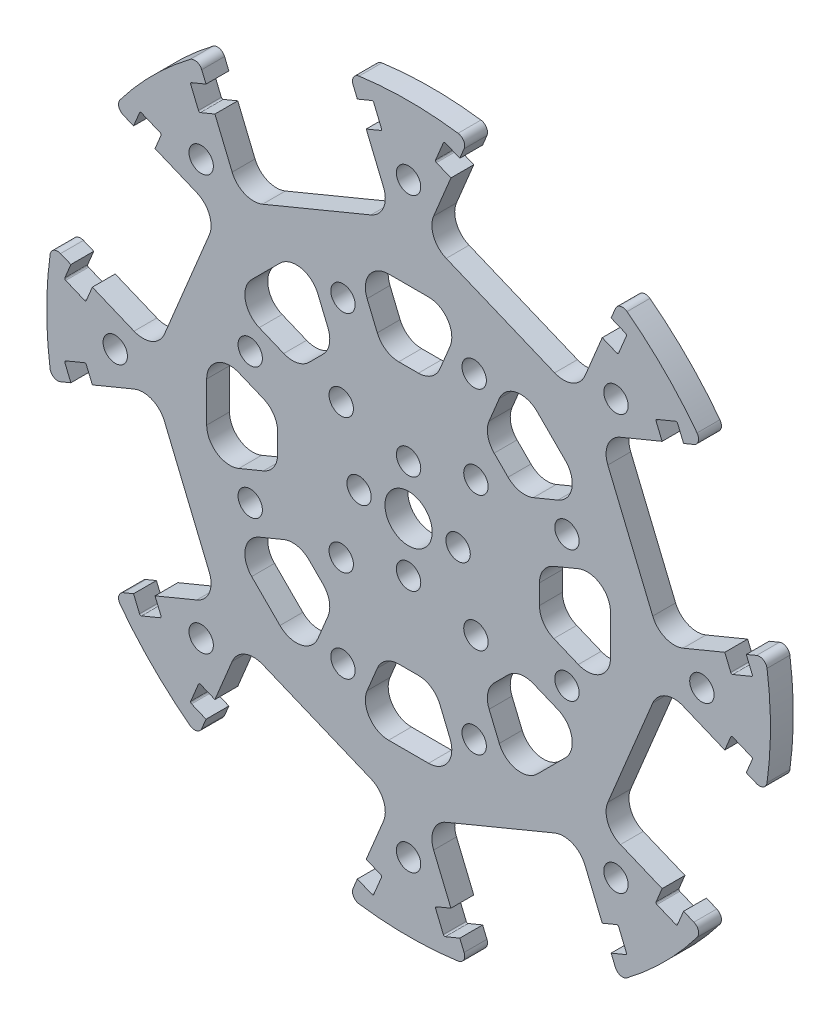
SolidWorks part; units mm, degrees
material "5052-H34"
ref_plane "正面" through (0, 0, 0) normal (0, 0, 1) x (1, 0, 0)
ref_plane "平面" through (0, 0, 0) normal (0, 1, 0) x (1, 0, 0)
ref_plane "右側面" through (0, 0, 0) normal (1, 0, 0) x (0, 0, -1)
sketch "ｽｹｯﾁ1" plane through (0, 0, 0) normal (0, 0, 1) x (1, 0, 0)
  circle A0 centre (0, 0) radius 47.5
  dimension "D1" = 95
extrude "ﾎﾞｽ - 押し出し1" add sketch "ｽｹｯﾁ1" along normal blind 3
sketch "ｽｹｯﾁ2" plane through (0, 0, 3) normal (0, 0, 1) x (1, 0, 0)
  line L0 (0, 0) -> (18.1775, 43.8843) construction
  line L1 (6.7246, 44.3257) -> (10.1592, 52.6175)
  line L2 (2.1228, 33.2161) -> (21.9862, 24.9884)
  line L3 (2.1228, 33.2161) -> (5.5574, 41.5079)
  line L4 (10.1592, 52.6175) -> (30.0226, 44.3898)
  line L5 (21.9862, 24.9884) -> (25.4208, 33.2802)
  line L6 (2.1228, 33.2161) -> (30.0226, 44.3898) construction
  line L7 (10.1592, 52.6175) -> (21.9862, 24.9884) construction
  line L8 (4.6459, 45.1867) -> (6.7246, 44.3257)
  line L9 (4.6459, 45.1867) -> (3.4787, 42.3689)
  line L10 (3.4787, 42.3689) -> (5.5574, 41.5079)
  line L11 (28.6667, 35.237) -> (27.4995, 32.4191)
  line L12 (4.6459, 45.1867) -> (27.4995, 32.4191) construction
  line L13 (3.4787, 42.3689) -> (28.6667, 35.237) construction
  line L14 (26.588, 36.098) -> (30.0226, 44.3898)
  line L15 (26.588, 36.098) -> (28.6667, 35.237)
  line L16 (0, 47.5) -> (0, 0) construction
  line L17 (25.4208, 33.2802) -> (27.4995, 32.4191)
  circle A0 centre (0, 0) radius 47.5 construction
  point P5 (16.0727, 38.8029)
  point P10 (16.0727, 38.8029)
  dimension "D1" = 42
  dimension "D2" = 21.5
  dimension "D3" = 21
  dimension "D4" = 3.05
  dimension "D5" = 26
  dimension "D6" = 22.5
extrude "ｶｯﾄ - 押し出し1" cut sketch "ｽｹｯﾁ2" against normal through all
sketch "ｽｹｯﾁ3" plane through (0, 0, 3) normal (0, 0, 1) x (1, 0, 0)
  line L1 (-8.8388, -8.8388) -> (8.8388, -8.8388) construction
  line L2 (-8.8388, -8.8388) -> (-8.8388, 8.8388) construction
  line L3 (-8.8388, 8.8388) -> (8.8388, 8.8388) construction
  line L4 (8.8388, -8.8388) -> (8.8388, 8.8388) construction
  line L5 (-8.8388, -8.8388) -> (8.8388, 8.8388) construction
  line L6 (-8.8388, 8.8388) -> (8.8388, -8.8388) construction
  circle A0 centre (0, 0) radius 3.1
  circle A1 centre (0, 0) radius 6.5 construction
  circle A2 centre (0, 6.5) radius 1.6
  circle A3 centre (6.5, 0) radius 1.6
  circle A4 centre (0, -6.5) radius 1.6
  circle A5 centre (-6.5, 0) radius 1.6
  circle A6 centre (0, 0) radius 12.5 construction
  circle A7 centre (8.8388, 8.8388) radius 1.6
  circle A8 centre (8.8388, -8.8388) radius 1.6
  circle A9 centre (-8.8388, -8.8388) radius 1.6
  circle A10 centre (-8.8388, 8.8388) radius 1.6
  dimension "D1" = 6.2
  dimension "D2" = 13
  dimension "D3" = 3.2
  dimension "D5" = 25
  dimension "D6" = 3.2
  dimension "D4" = 4
  dimension "D7" = 4
extrude "ｶｯﾄ - 押し出し2" cut sketch "ｽｹｯﾁ3" against normal through all and the other way through all
sketch "ｽｹｯﾁ4" plane through (0, 0, 3) normal (0, 0, 1) x (1, 0, 0)
  line L0 (0, 38.5) -> (0, 0) construction
  line L1 (8.6104, 20.7873) -> (0, 0) construction
  line L2 (0, 0) -> (27.2236, 27.2236) construction
  circle A0 centre (0, 0) radius 22.5 construction
  circle A1 centre (0, 0) radius 38.5 construction
  circle A2 centre (27.2236, 27.2236) radius 1.6
  circle A3 centre (8.6104, 20.7873) radius 1.6
  dimension "D1" = 45
  dimension "D2" = 77
  dimension "D4" = 3.2
  dimension "D3" = 22.5
  dimension "D5" = 45
extrude "ｶｯﾄ - 押し出し3" cut sketch "ｽｹｯﾁ4" against normal through all
sketch "ｽｹｯﾁ5" plane through (0, 0, 3) normal (0, 0, 1) x (1, 0, 0)
  line L0 (0, 0) -> (8.6104, 20.7873) construction
  line L2 (2.1228, 33.2161) -> (21.9862, 24.9884) construction
  line L3 (7.1883, 26.5) -> (-7.1883, 26.5)
  line L4 (3.3281, 17.1806) -> (7.1883, 26.5)
  line L5 (0, 47.5) -> (0, 0) construction
  line L6 (2.1228, 33.2161) -> (21.9862, 24.9884)
  line L9 (3.3281, 17.1806) -> (-3.3281, 17.1806)
  line L10 (-3.3281, 17.1806) -> (-7.1883, 26.5)
  circle A0 centre (0, 0) radius 17.5 construction
  arc A1 (7.7741, 46.8595) -> (27.6375, 38.6318) centre (0, 0) ccw construction
  dimension "D3" = 35
  dimension "D2" = 26.5
  dimension "D1" = 3.5
extrude "ｶｯﾄ - 押し出し4" cut sketch "ｽｹｯﾁ5" against normal through all and the other way through all contours L10 L9 L4 L3 region at (0, 22.4105, 3)
fillet "ﾌｨﾚｯﾄ1" radius 1 2 edges at (27.6375, 38.6318, 1.5) (7.7741, 46.8595, 1.5)
fillet "ﾌｨﾚｯﾄ2" radius 0.2 4 edges at (28.6667, 35.237, 1.5) (27.4995, 32.4191, 1.5) (4.6459, 45.1867, 1.5) (3.4787, 42.3689, 1.5)
fillet "ﾌｨﾚｯﾄ3" radius 3.05 2 edges at (21.9862, 24.9884, 1.5) (2.1228, 33.2161, 1.5)
fillet "ﾌｨﾚｯﾄ4" radius 3.05 4 edges at (7.1883, 26.5, 1.5) (-7.1883, 26.5, 1.5) (3.3281, 17.1806, 1.5) (-3.3281, 17.1806, 1.5)
ref_axis "軸1" through (0, 0, 0) along (0, 0, 1)
pattern_circular "円形ﾊﾟﾀｰﾝ1" count 8 over 360 about axis through (0, 0, 0) along (0, 0, 1) of "ｶｯﾄ - 押し出し1", "ﾌｨﾚｯﾄ1", "ｶｯﾄ - 押し出し4", "ｶｯﾄ - 押し出し3", "ﾌｨﾚｯﾄ2", "ﾌｨﾚｯﾄ3", "ﾌｨﾚｯﾄ4"
